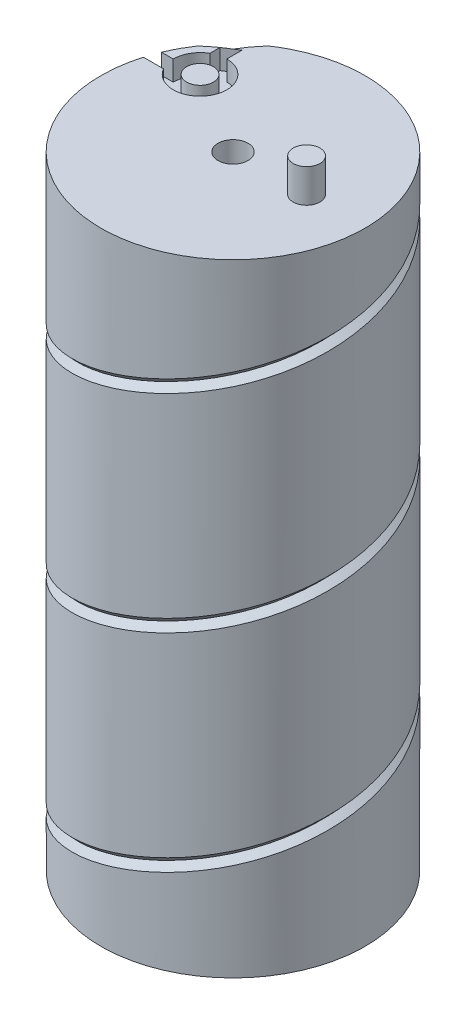
SolidWorks part; units mm, degrees
ref_plane "Front Plane" through (0, 0, 0) normal (0, 0, 1) x (1, 0, 0)
ref_plane "Top Plane" through (0, 0, 0) normal (0, 1, 0) x (1, 0, 0)
ref_plane "Right Plane" through (0, 0, 0) normal (1, 0, 0) x (0, 0, -1)
sketch "Sketch1" plane through (0, 0, 0) normal (0, 1, 0) x (1, 0, 0)
  line L0 (-19.75, 0) -> (19.75, 0) construction
  circle A0 centre (0, 0) radius 19.75
  dimension "D1" = 39.5
curve "Helix - Antenna Guide" pitch 31 height 93 radius 19.75 centre (0, 0, 0) axis (0, 1, 0) start towards (0, 0, 1)
extrude "Extrude - Main Body" add sketch "Sketch1<2>" along normal blind 93
sketch "Sketch1<2>" plane through (0, 0, 0) normal (0, 1, 0) x (1, 0, 0) same geometry as "Sketch1"
ref_point "Point2"
ref_point "Point1"
ref_plane "Plane1" through (-13.9654, 0, -13.9654) normal (-0.686, 0.2424, 0.686) x (-0.7276, -0.2285, -0.6468)
sketch "Sketch15" plane through (-13.9654, 0, -13.9654) normal (-0.686, 0.2424, 0.686) x (-0.7276, -0.2285, -0.6468)
  line L4 (0, 0) -> (0.2165, 0.8934)
  line L5 (0.2165, 0.8934) -> (-0.8934, 0.2165)
  line L8 (0, 0) -> (-0.2165, -0.8934)
  line L9 (-0.2165, -0.8934) -> (-0.8934, 0.2165)
  point P7 (-0.5549, -0.3384)
  dimension "D1" = 0.65
  dimension "D2" = 90
sweep "Cut - Antenna Wire Guide" cut profiles "Sketch15" path "Helix - Antenna Guide" align with end faces yes
sketch "Sketch23" plane through (0, 0, 0) normal (0, -1, 0) x (1, 0, 0)
  line L0 (-13.3154, -13.3154) -> (-8.3849, -14.1466)
  line L1 (-9.335, -17.4046) -> (-10.0329, -12.4535)
  arc A0 (-11.0473, -16.3713) -> (-16.3713, -11.0473) centre (0, 0) ccw construction
  arc A1 (-10.0329, -12.4535) -> (-8.3849, -14.1466) centre (-8.0525, -12.1744) cw
  arc A2 (-9.335, -17.4046) -> (-13.3154, -13.3154) centre (-14.1184, -18.0788) cw
  dimension "D2" = 2
  dimension "D1" = 2
  dimension "D3" = 5
  dimension "D4" = 5
ref_plane "Plane - Anchor Loop Exit" through (-9.335, 0, -17.4046) normal (-0.1396, 0, 0.9902) x (0.9902, 0, 0.1396)
ref_plane "Plane - Anchor Loop Peg" through (-10.0329, 0, -12.4535) normal (-0.1396, 0, 0.9902) x (0.9902, 0, 0.1396)
sketch "Sketch28" plane through (0, 93, 0) normal (0, 1, 0) x (1, 0, 0)
  circle A0 centre (11, 0) radius 2
  point P0 (0, 0)
  dimension "D1" = 4
  dimension "D2" = 11
extrude "Extruded Peg" add sketch "Sketch28" along normal blind 5
hole_wizard "Hole for Threaded Rod" positions "Sketch29" profile "Sketch30" hole size "#8" standard "ANSI Inch" end condition through all
sketch "Sketch29" plane through (0, 93, 0) normal (0, 1, 0) x (1, 0, 0)
  point P0 (0, 0)
sketch "Sketch30" plane through (0, 93, 0) normal (1, 0, 0) x (0, 0, 1)
  line L0 (0, 0) -> (0, 94.4693)
  line L1 (0, 94.4693) -> (2.2479, 94.4693)
  line L2 (2.2479, 94.4693) -> (2.2479, 0)
  line L5 (2.2479, 0) -> (0, 0)
  line L11 (0, -6.35) -> (0, 107.95) construction
  dimension "Thru Hole Dia." = 4.4958
  dimension "Thru Hole Depth" = 94.4693
sketch "Sketch31" plane through (0, 0, 0) normal (0, -1, 0) x (1, 0, 0)
  circle A0 centre (11, 0) radius 2.25
  dimension "D1" = 4.5
  dimension "D2" = 11
extrude "Cut Peg" cut sketch "Sketch31" against normal blind 5.5
sketch "Sketch36" plane through (0, 93, 0) normal (0, 1, 0) x (1, 0, 0)
  line L0 (-12.4964, 13.8462) -> (-12.4964, 11.5721)
  line L1 (-15.9546, 5.5618) -> (-18.9546, 5.5618)
  line L2 (-14.4964, 12.5498) -> (-14.4964, 11.0362)
  line L3 (-16.4964, 7.5618) -> (-18.2491, 7.5618)
  line L5 (-13.3154, 13.3154) -> (-14.4964, 12.5498)
  line L6 (-13.3154, 13.3154) -> (-12.4964, 13.8462)
  circle A0 centre (-12.4964, 7.5721) radius 2
  arc A1 (-14.4964, 11.0362) -> (-16.4964, 7.5618) centre (-12.4964, 7.5721) ccw
  arc A2 (-16.3744, 11.0494) -> (-11.0494, 16.3744) centre (0, 0) ccw construction
  arc A4 (-15.9546, 5.5618) -> (-12.4964, 11.5721) centre (-12.4964, 7.5721) ccw
  arc A5 (-18.2491, 7.5618) -> (-18.9546, 5.5618) centre (0, 0) ccw
  spline S0 degree 3 poles (-16.3728, 11.0484) (-15.4319, 11.9033) (-14.4071, 12.6638) (-13.3154, 13.3154) knots 0 0 0 0 1 1 1 1 construction
  dimension "D1" = 2
  dimension "D2" = 4
  dimension "D4" = 3
  dimension "D5" = 2
  dimension "D6" = 2
  dimension "D8" = 180
extrude "Cut-Extrude1" cut sketch "Sketch36" against normal blind 3
equation "\"pegD\"=10"
equation "\"pegHoleD\"=0.5"
equation "\"pegHoleOffset\"=0.5"
